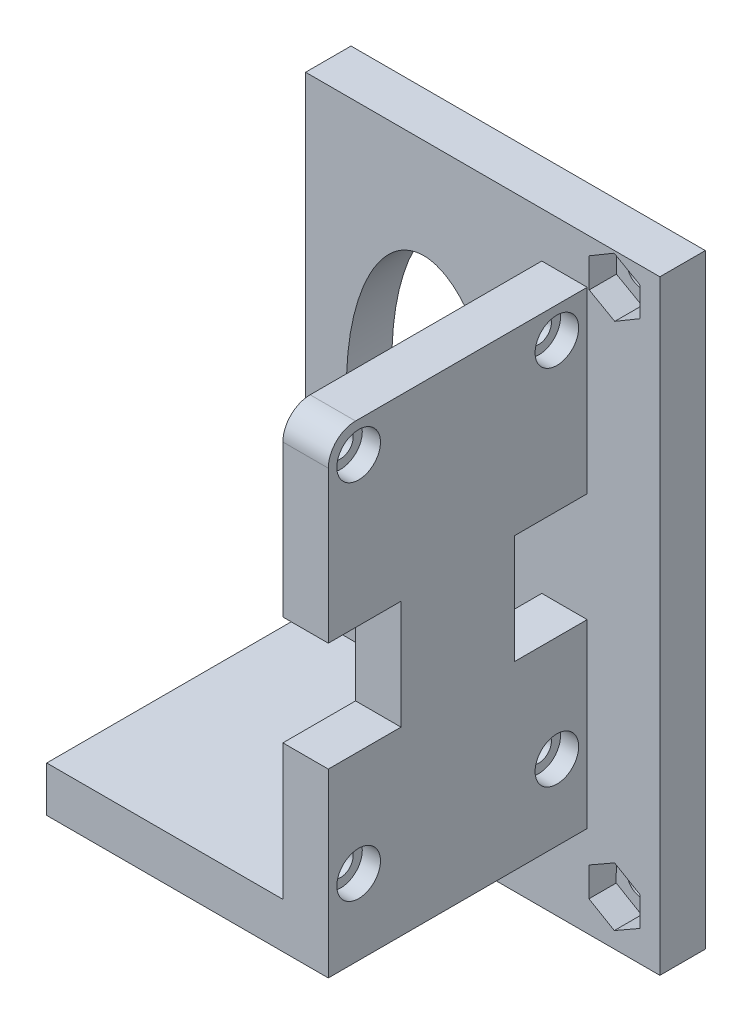
SolidWorks part; units mm, degrees
ref_plane "Front Plane" through (0, 0, 0) normal (0, 0, 1) x (1, 0, 0)
ref_plane "Top Plane" through (0, 0, 0) normal (0, 1, 0) x (1, 0, 0)
ref_plane "Right Plane" through (0, 0, 0) normal (1, 0, 0) x (0, 0, -1)
sketch "Sketch1" plane through (0, 0, 0) normal (0, 0, 1) x (1, 0, 0)
  line L0 (-12.0242, -12.421) -> (-12.0242, 34.179) construction
  line L1 (-46.0242, 34.179) -> (-7.0242, 34.179) construction
  line L2 (-46.0242, 34.179) -> (-46.0242, -25.421)
  line L3 (-46.0242, -25.421) -> (-7.0242, -25.421)
  line L4 (-7.0242, 34.179) -> (-7.0242, -25.421)
  line L5 (-12.0242, -12.421) -> (-46.0242, -12.421) construction
  line L6 (-46.0242, -12.421) -> (-46.0242, -15.421)
  line L7 (-46.0242, -15.421) -> (-7.0242, -15.421) construction
  line L8 (-46.0242, 34.179) -> (-46.0242, 41.179)
  line L9 (-46.0242, 41.179) -> (-7.0242, 41.179)
  line L10 (-7.0242, 41.179) -> (-7.0242, 34.179)
  line L11 (-7.0242, 37.679) -> (-46.0242, 37.679) construction
  line L12 (-46.0242, -15.421) -> (-46.0242, -25.421)
  line L13 (-46.0242, -20.421) -> (-7.0242, -20.421) construction
  line L14 (-26.5242, -25.421) -> (-26.5242, -15.421) construction
  line L15 (-41.0084, -23.6541) -> (-43.8163, -22.0512)
  line L16 (-14.8408, 39.2665) -> (-14.8073, 36.0335)
  line L17 (-14.8073, 36.0335) -> (-11.9907, 34.446)
  line L18 (-11.9907, 34.446) -> (-9.2076, 36.0915)
  line L19 (-9.2076, 36.0915) -> (-9.2411, 39.3245)
  line L20 (-9.2411, 39.3245) -> (-12.0576, 40.912)
  line L21 (-12.0576, 40.912) -> (-14.8408, 39.2665)
  line L22 (-9.2321, -22.0512) -> (-9.2163, -18.8181)
  line L23 (-9.2163, -18.8181) -> (-12.0084, -17.1879)
  line L24 (-12.0084, -17.1879) -> (-14.8163, -18.7908)
  line L25 (-14.8163, -18.7908) -> (-14.832, -22.0239)
  line L26 (-14.832, -22.0239) -> (-12.0399, -23.6541)
  line L27 (-12.0399, -23.6541) -> (-9.2321, -22.0512)
  line L28 (-38.2163, -22.0239) -> (-41.0084, -23.6541)
  line L29 (-38.2321, -18.7908) -> (-38.2163, -22.0239)
  line L30 (-41.0399, -17.1879) -> (-38.2321, -18.7908)
  line L31 (-43.832, -18.8181) -> (-41.0399, -17.1879)
  line L32 (-43.8163, -22.0512) -> (-43.832, -18.8181)
  line L33 (-15.0242, -15.421) -> (-15.0242, 36.179)
  line L34 (-15.0242, -15.421) -> (-46.0242, -15.421)
  line L35 (-46.0242, -10.421) -> (-20.0242, -10.421)
  line L36 (-20.0242, -10.421) -> (-20.0242, 36.179)
  line L37 (-15.0242, 36.179) -> (-20.0242, 36.179)
  circle A2 centre (-41.0242, -20.421) radius 2.75 construction
  circle A3 centre (-12.0242, 37.679) radius 1.625
  circle A4 centre (-12.0242, -20.421) radius 1.625
  circle A5 centre (-41.0242, -20.421) radius 1.625
  circle A6 centre (-12.0242, 37.679) radius 2.8 construction
  circle A7 centre (-12.0242, -20.421) radius 2.8 construction
  ellipse E0 centre (-33.0242, 13.579) end of major axis (-33.0242, 30.1945) minor radius 8.5
  dimension "D7" = 5.6
  dimension "D9" = 5.6
  dimension "D10" = 3.25
  dimension "D11" = 3.25
  dimension "D13" = 5
  dimension "D2" = 10
  dimension "D3" = 5
  dimension "D4" = 3
  dimension "D5" = 46.6
  dimension "D6" = 7
  dimension "D8" = 66.6
  dimension "D12" = 39
  dimension "D14" = 5
  dimension "D15" = 8
  dimension "D16" = 2
  dimension "D17" = 5
  dimension "D18" = 2
  dimension "D21" = 24
extrude "Boss-Extrude1" add sketch "Sketch1" along normal blind 5 contours L2 L7 L4 L1 L5 | L5 L1 L2 | L10 L9 L8 L1 | L7 L2 L3 L4 | A2 A5 | A4 | A3 region at (-45.2524, 37.679, 0) region at (-33.0242, -11.023, 0) region at (-42.3699, -22.7783, 0) region at (-13.4056, 40.0154, 0) region at (-10.6785, -22.7783, 0)
extrude "Boss-Extrude3" add sketch "Sketch1<3>" along direction (0, 0, 1) on the side of the normal offset from surface (33.5 mm away) 28.5 contours L36 L35 L2 L34 L33 L9 region at (-33.0242, -11.023, 0) up to face at (-26.5242, 7.879, 5) offset beyond the face yes
sketch "Sketch1<3>" plane through (0, 0, 0) normal (0, 0, 1) x (1, 0, 0) same geometry as "Sketch1"
sketch "Sketch3" plane through (-15.0242, 0, 0) normal (1, 0, 0) x (0, 0, -1)
  line L0 (-33.5, 36.179) -> (-33.5, -10.5042) construction
  line L1 (-33.5, -10.5042) -> (-5, -10.5042) construction
  line L2 (-5, -10.5042) -> (-5, 36.179) construction
  line L3 (-5, 36.179) -> (-33.5, 36.179) construction
  line L4 (-19.25, 36.179) -> (-19.25, -10.5042) construction
  line L5 (-33.5, 12.8374) -> (-5, 12.8374) construction
  line L6 (-33.5, -15.421) -> (-33.5, 36.179) construction
  line L7 (-5, 4.4958) -> (-13, 4.4958)
  line L8 (-13, 4.4958) -> (-13, 16.4958)
  line L9 (-33.5, 36.179) -> (-5, 36.179) construction
  line L10 (-13, 16.4958) -> (-5, 16.4958)
  line L11 (-5, 16.4958) -> (-5, 4.4958)
  line L12 (-33.5, 16.4958) -> (-33.5, 4.4958)
  line L13 (-25.5, 16.4958) -> (-33.5, 16.4958)
  line L14 (-25.5, 4.4958) -> (-25.5, 16.4958)
  line L15 (-33.5, 4.4958) -> (-25.5, 4.4958)
  circle A0 centre (-30.1598, 32.7958) radius 2.4
  circle A1 centre (-30.1598, 32.7958) radius 1.4
  circle A2 centre (-8.3402, 32.7958) radius 1.4
  circle A3 centre (-8.3402, -7.121) radius 1.4
  circle A4 centre (-30.1598, -7.121) radius 1.4
  circle A5 centre (-8.3402, 32.7958) radius 2.4
  circle A6 centre (-8.3402, -7.121) radius 2.4
  circle A7 centre (-30.1598, -7.121) radius 2.4
  line M10 (-5, -15.421) -> (-5, 36.179)
  line M12 (-33.5, 36.179) -> (-33.5, -15.421)
  dimension "D1" = 2.8
  dimension "D2" = 4.8
  dimension "D3" = 3.3832
  dimension "D4" = 3.3402
  dimension "D5" = 28.5
  dimension "D6" = 46.6832
  dimension "D7" = 15
  dimension "D8" = 12
  dimension "D9" = 8
extrude "Cut-Extrude5" cut sketch "Sketch1<6>" against normal blind 3 from surface contours A3 | A4 | A2 A5 region at (-42.3699, -22.7783, 0) region at (-13.4056, 40.0154, 0) region at (-10.6785, -22.7783, 0) starting at face at (-26.8242, 5.219, 5)
sketch "Sketch1<6>" plane through (0, 0, 0) normal (0, 0, 1) x (1, 0, 0) same geometry as "Sketch1"
fillet "Fillet1" radius 3 1 edges at (-17.5242, 36.179, 33.5)
extrude "Cut-Extrude6" cut sketch "Sketch3" against normal through all contours A1 | A2 | A3 | A4 | L15 L14 L13 M12 | L10 L8 L7 M10 region at (-15.0242, 10.4958, 9) region at (-15.0242, 10.4958, 29.5) region at (-15.0242, 32.7958, 30.1598) region at (-15.0242, 32.7958, 8.3402) region at (-15.0242, -7.121, 8.3402) region at (-15.0242, -7.121, 30.1598)
extrude "Cut-Extrude7" cut sketch "Sketch3<3>" against normal blind 2 contours A5 A2 | A0 A1 | A7 A4 | A6 A3 region at (-15.0242, 32.7958, 32.4919) region at (-15.0242, 32.7958, 10.6723) region at (-15.0242, -7.121, 10.6723) region at (-15.0242, -7.121, 32.4919)
sketch "Sketch3<3>" plane through (-15.0242, 0, 0) normal (1, 0, 0) x (0, 0, -1) same geometry as "Sketch3"
